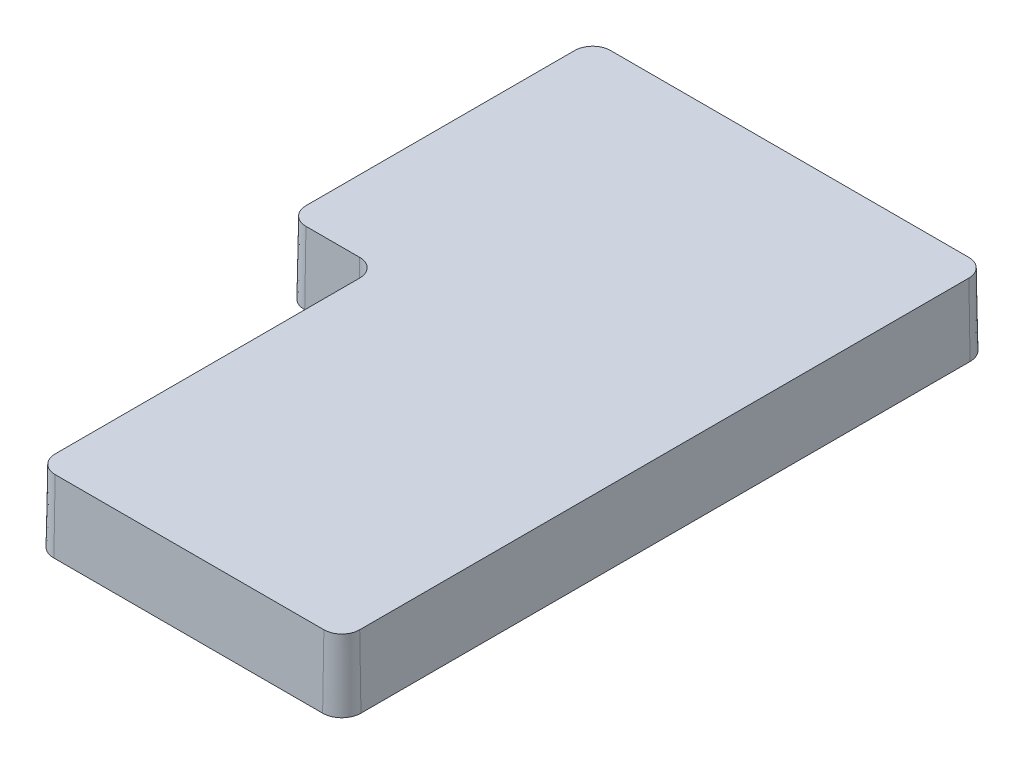
SolidWorks part; units mm, degrees
ref_plane "Front Plane" through (0, 0, 0) normal (0, 0, 1) x (1, 0, 0)
ref_plane "Top Plane" through (0, 0, 0) normal (0, 1, 0) x (1, 0, 0)
ref_plane "Right Plane" through (0, 0, 0) normal (1, 0, 0) x (0, 0, -1)
ref_plane "Right_New_Plane" through (-0.69, 0, 0) normal (1, 0, 0) x (0, 0, -1)
sketch "Sketch1" plane through (0, 0, 0) normal (0, 1, 0) x (1, 0, 0)
  line L0 (9.3071, 15.4536) -> (-10.6929, 15.4536)
  line L1 (10.3071, -19.5464) -> (10.3071, 14.4536)
  line L2 (-5.6929, -20.5464) -> (9.3071, -20.5464)
  line L3 (-6.6929, -2.5464) -> (-6.6929, -19.5464)
  line L4 (-10.6929, -1.5464) -> (-7.6929, -1.5464)
  line L5 (-11.6929, 14.4536) -> (-11.6929, -0.5464)
  line L6 (-55, 0) -> (55, 0) construction
  line L7 (0, -55) -> (0, 55) construction
  line L8 (-0.6929, 15.4536) -> (-0.69, -20.5464) construction
  line L9 (-0.69, -55) -> (-0.69, 55) construction
  line L10 (10.3071, -2.5464) -> (-6.6929, -2.5464) construction
  arc A0 (-10.6929, 15.4536) -> (-11.6929, 14.4536) centre (-10.6929, 14.4536) ccw
  arc A1 (10.3071, 14.4536) -> (9.3071, 15.4536) centre (9.3071, 14.4536) ccw
  arc A2 (9.3071, -20.5464) -> (10.3071, -19.5464) centre (9.3071, -19.5464) ccw
  arc A3 (-6.6929, -19.5464) -> (-5.6929, -20.5464) centre (-5.6929, -19.5464) ccw
  arc A4 (-6.6929, -2.5464) -> (-7.6929, -1.5464) centre (-7.6929, -2.5464) ccw
  arc A5 (-11.6929, -0.5464) -> (-10.6929, -1.5464) centre (-10.6929, -0.5464) ccw
  dimension "D1" = 15.4536
  dimension "D2" = 36
  dimension "D3" = 22
  dimension "D4" = 10.3071
  dimension "D5" = 15
extrude "Boss-Extrude1" add sketch "Sketch1" against normal blind 4 draft 1 draft outward yes
shell "Shell1" thickness 0.5 removed face at (-2.7069, -4, 2.2271)
sketch "Sketch2" plane through (0, -0.5, 0) normal (0, -1, 0) x (-1, 0, 0)
  line L3 (-4.877, 10.1234) -> (-4.877, 6.5234) construction
  line L5 (5.6627, 8.8972) -> (5.6627, 6.5578)
  line L11 (-9.377, -14.6162) -> (-6.977, -14.6162) construction
  line L13 (-0.2373, -14.6162) -> (2.1627, -14.6162) construction
  line L17 (-5.477, 12.4628) -> (-5.477, 10.1234)
  line L19 (-6.977, -11.6768) -> (-6.977, -14.0162)
  line L21 (5.6627, 12.4366) -> (5.6627, 10.0972)
  line L23 (2.1627, -11.6768) -> (2.1627, -14.0162)
  line L25 (-4.277, 12.4628) -> (-4.277, 10.1234)
  line L26 (6.8627, 12.4366) -> (6.8627, 10.0972)
  line L27 (-5.777, -11.6768) -> (-5.777, -14.0162)
  line L28 (3.3627, -11.6768) -> (3.3627, -14.0162)
  line L31 (-9.3164, -15.2162) -> (-6.977, -15.2162)
  line L33 (-0.1767, -15.2162) -> (2.1627, -15.2162)
  line L35 (-9.3164, -14.0162) -> (-6.977, -14.0162)
  line L36 (-0.1767, -14.0162) -> (2.1627, -14.0162)
  line L37 (-5.777, -14.0162) -> (-3.4376, -14.0162)
  line L38 (-6.377, -14.6162) -> (-6.377, -15.2162) construction
  line L39 (-5.777, -15.2162) -> (-3.4376, -15.2162)
  line L40 (-6.977, -15.2162) -> (-6.977, -17.5556)
  line L41 (-5.777, -14.6162) -> (-3.377, -14.6162) construction
  line L42 (-5.777, -15.2162) -> (-5.777, -17.5556)
  line L43 (2.1627, -15.2162) -> (2.1627, -17.5556)
  line L44 (2.7627, -14.6162) -> (3.3627, -14.6162) construction
  line L45 (3.3627, -15.2162) -> (3.3627, -17.5556)
  line L46 (3.3627, -14.0162) -> (5.7021, -14.0162)
  line L47 (2.7627, -14.6162) -> (2.7627, -15.2162) construction
  line L48 (3.3627, -15.2162) -> (5.7021, -15.2162)
  line L49 (-7.8164, 8.9234) -> (-5.477, 8.9234)
  line L50 (3.3233, 8.8972) -> (5.6627, 8.8972)
  line L51 (3.3233, 10.0972) -> (5.6627, 10.0972)
  line L52 (-7.8164, 10.1234) -> (-5.477, 10.1234)
  line L53 (-4.277, 10.1234) -> (-1.9376, 10.1234)
  line L54 (-5.477, 8.9234) -> (-5.477, 6.5841)
  line L55 (-4.277, 8.9234) -> (-1.9376, 8.9234)
  line L56 (-4.277, 8.9234) -> (-4.277, 6.5841)
  line L57 (6.8627, 8.8972) -> (9.2021, 8.8972)
  line L58 (6.8627, 8.8972) -> (6.8627, 6.5578)
  line L59 (6.8627, 10.0972) -> (9.2021, 10.0972)
  arc A16 (-5.477, 12.4628) -> (-7.8164, 10.1234) centre (-4.877, 9.5234) ccw
  arc A17 (9.2021, 10.0972) -> (6.8627, 12.4366) centre (6.2627, 9.4972) ccw
  arc A18 (-3.4376, -14.0162) -> (-5.777, -11.6768) centre (-6.377, -14.6162) ccw
  arc A19 (-0.1767, -15.2162) -> (2.1627, -17.5556) centre (2.7627, -14.6162) ccw
  arc A20 (-9.3164, -15.2162) -> (-6.977, -17.5556) centre (-6.377, -14.6162) ccw
  arc A21 (-6.977, -11.6768) -> (-9.3164, -14.0162) centre (-6.377, -14.6162) ccw
  arc A22 (-5.777, -17.5556) -> (-3.4376, -15.2162) centre (-6.377, -14.6162) ccw
  arc A23 (3.3627, -17.5556) -> (5.7021, -15.2162) centre (2.7627, -14.6162) ccw
  arc A24 (2.1627, -11.6768) -> (-0.1767, -14.0162) centre (2.7627, -14.6162) ccw
  arc A25 (5.7021, -14.0162) -> (3.3627, -11.6768) centre (2.7627, -14.6162) ccw
  arc A26 (-1.9376, 10.1234) -> (-4.277, 12.4628) centre (-4.877, 9.5234) ccw
  arc A27 (-7.8164, 8.9234) -> (-5.477, 6.5841) centre (-4.877, 9.5234) ccw
  arc A28 (-4.277, 6.5841) -> (-1.9376, 8.9234) centre (-4.877, 9.5234) ccw
  arc A29 (6.8627, 6.5578) -> (9.2021, 8.8972) centre (6.2627, 9.4972) ccw
  arc A30 (3.3233, 8.8972) -> (5.6627, 6.5578) centre (6.2627, 9.4972) ccw
  arc A31 (5.6627, 12.4366) -> (3.3233, 10.0972) centre (6.2627, 9.4972) ccw
  dimension "D4" = 0.6
  dimension "D5" = 0.6
extrude "Boss-Extrude2" add sketch "Sketch2" along normal blind 4 draft 1.5
ref_plane "Plane2" through (0, 0, 2.5464) normal (0, 0, 1) x (1, 0, 0)
